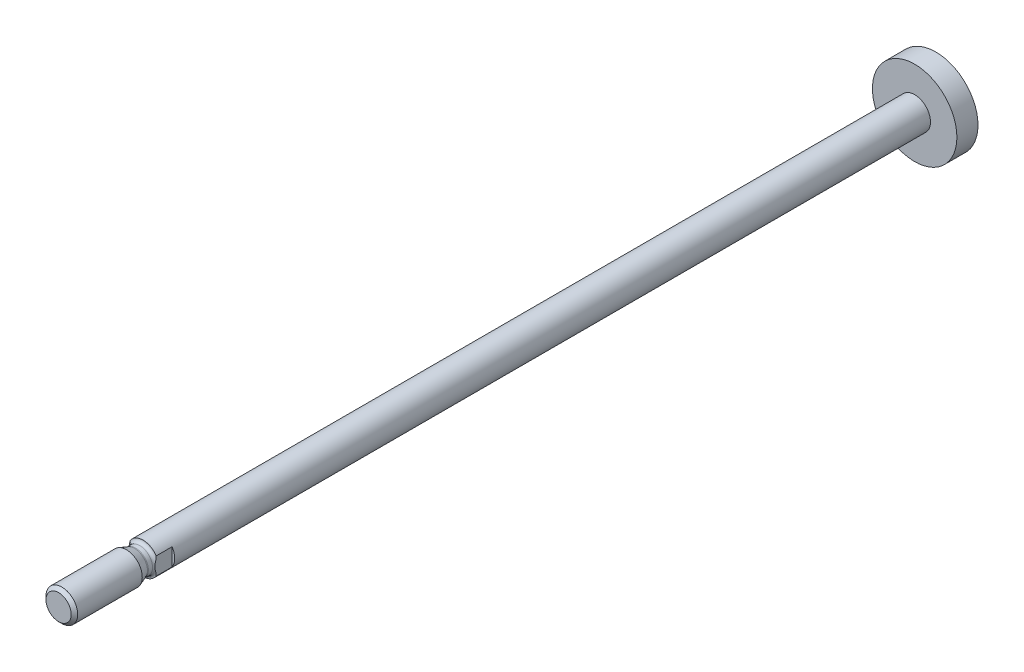
SolidWorks part; units mm, degrees
ref_plane "Ebene vorne" through (0, 0, 0) normal (0, 0, 1) x (1, 0, 0)
ref_plane "Ebene oben" through (0, 0, 0) normal (0, 1, 0) x (1, 0, 0)
ref_plane "Ebene rechts" through (0, 0, 0) normal (1, 0, 0) x (0, 0, -1)
sketch "Skizze1" plane through (0, 0, 0) normal (1, 0, 0) x (0, 0, -1)
  line L0 (-5, 0) -> (-5, 3)
  line L1 (-5, 3) -> (141.2, 3)
  line L2 (141.2, 3) -> (141.2, 8)
  line L3 (141.2, 8) -> (145.2, 8)
  line L4 (145.2, 8) -> (145.2, 0)
  line L5 (145.2, 0) -> (-5, 0)
  line L6 (145.2, 0) -> (-5, 0) construction
revolve "Rotation1" add sketch "Skizze1" angle 360 about L6 reverse direction yes
sketch "Skizze2" plane through (0, 0, 0) normal (1, 0, 0) x (0, 0, -1)
  line L0 (-21, 0) -> (-21, 2.3865)
  line L1 (-21, 2.3865) -> (-20.3865, 3)
  line L2 (-20.3865, 3) -> (-8.1485, 3)
  line L3 (-8.1485, 3) -> (-6.5994, 2.4362)
  line L4 (-6.3942, 2.4) -> (-5.6, 2.4)
  line L5 (-5, 3) -> (-4, 3)
  line L6 (-4, 3) -> (-4, 0)
  line L7 (-4, 0) -> (-21, 0)
  line L8 (-4, 0) -> (-21, 0) construction
  arc A0 (-6.5994, 2.4362) -> (-6.3942, 2.4) centre (-6.3942, 3) ccw
  arc A1 (-5.6, 2.4) -> (-5, 3) centre (-5.6, 3) ccw
revolve "Rotation2" add sketch "Skizze2" angle 360 about L8 reverse direction yes
cosmetic thread "Gewindedarstellung1" parameters "D1"=12.8515, "D2"=4.773
ref_plane "Ebene1" through (0, 0, 5) normal (0, 0, 1) x (1, 0, 0)
ref_plane "Ebene2" through (0, 0, 2) normal (0, 0, 1) x (1, 0, 0)
sketch "Skizze3" plane through (0, 0, 2) normal (0, 0, 1) x (1, 0, 0)
  line L0 (-5, 10) -> (-5, -5)
  line L1 (-5, -5) -> (-2.5, -5)
  line L2 (-2.5, -5) -> (-2.5, 5)
  line L3 (-2.5, 5) -> (2.5, 5)
  line L4 (2.5, 5) -> (2.5, -5)
  line L5 (2.5, -5) -> (5, -5)
  line L6 (5, -5) -> (5, 10)
  line L7 (5, 10) -> (-5, 10)
extrude "Schnitt-Linear austragen1" cut sketch "Skizze3" along normal blind 4
ref_plane "Ebene3" through (0, 0, -295) normal (0, 0, 1) x (1, 0, 0)
ref_plane "Ebene4" through (0, 0, 16) normal (0, 0, 1) x (1, 0, 0)
ref_plane "Ebene5" through (0, 0, 11.2) normal (0, 0, 1) x (1, 0, 0)
ref_plane "FDT_KSAUFSATZ XY" through (0, 0, 11.2) normal (0, 0, 1) x (1, 0, 0)
ref_plane "FDT_KSAUFSATZ XZ" through (0, 0, 0) normal (0, 1, 0) x (1, 0, 0)
ref_plane "FDT_KSAUFSATZ YZ" through (0, 0, 0) normal (-1, 0, 0) x (0, 0, 1)
ref_axis "FDT_KSAUFSATZ X" through (80.9, 0, 11.2) along (-1, 0, 0)
ref_axis "FDT_KSAUFSATZ Y" through (0, 50, 11.2) along (0, -1, 0)
ref_axis "FDT_KSAUFSATZ Z" through (0, 0, 80.9) along (0, 0, -1)
sketch3d "FDT_KSAUFSATZ"
  point P0 (0, 0, 11.2)
ref_plane "FDT_NUT XY" through (0, 0, 11.2) normal (0, 0, 1) x (1, 0, 0)
ref_plane "FDT_NUT XZ" through (0, 0, 0) normal (0, 1, 0) x (1, 0, 0)
ref_plane "FDT_NUT YZ" through (0, 0, 0) normal (-1, 0, 0) x (0, 0, 1)
ref_axis "FDT_NUT X" through (80.9, 0, 11.2) along (-1, 0, 0)
ref_axis "FDT_NUT Y" through (0, 50, 11.2) along (0, -1, 0)
ref_axis "FDT_NUT Z" through (0, 0, 80.9) along (0, 0, -1)
sketch3d "FDT_NUT"
  point P0 (0, 0, 11.2)
ref_plane "KS XY" through (0, 0, 0) normal (0, 0, -1) x (-1, 0, 0)
ref_plane "KS XZ" through (0, 0, 0) normal (0, 1, 0) x (1, 0, 0)
ref_plane "KS YZ" through (0, 0, 0) normal (1, 0, 0) x (0, 0, -1)
ref_axis "KS X" through (-80.9, 0, 0) along (1, 0, 0)
ref_axis "KS Y" through (0, 50, 0) along (0, -1, 0)
ref_axis "KS Z" through (0, 0, -80.9) along (0, 0, 1)
sketch3d "KS"
  point P0 (0, 0, 0)
ref_plane "NUT1 XY" through (0, 0, 16) normal (0, 0, 1) x (1, 0, 0)
ref_plane "NUT1 XZ" through (0, 0, 0) normal (0, -1, 0) x (-1, 0, 0)
ref_plane "NUT1 YZ" through (0, 0, 0) normal (1, 0, 0) x (0, 0, -1)
ref_axis "NUT1 X" through (-80.9, 0, 16) along (1, 0, 0)
ref_axis "NUT1 Y" through (0, -50, 16) along (0, 1, 0)
ref_axis "NUT1 Z" through (0, 0, 80.9) along (0, 0, -1)
sketch3d "NUT1"
  point P0 (0, 0, 16)
